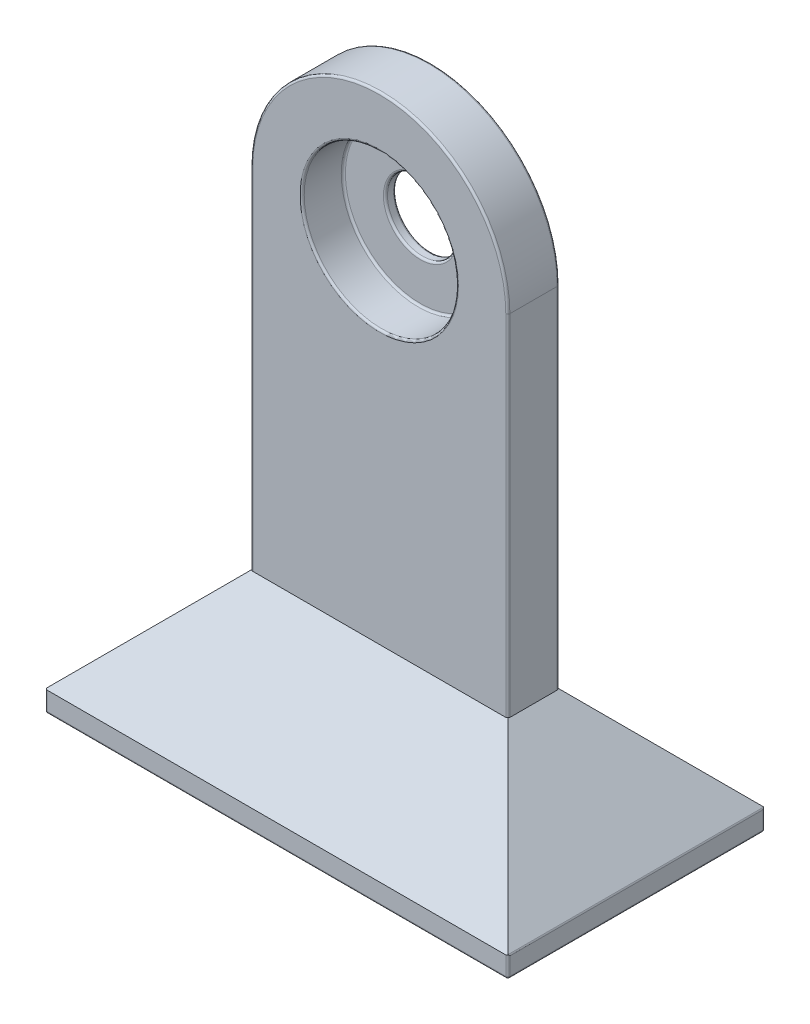
SolidWorks part; units mm, degrees
ref_plane "Front Plane" through (0, 0, 0) normal (0, 0, 1) x (1, 0, 0)
ref_plane "Top Plane" through (0, 0, 0) normal (0, 1, 0) x (1, 0, 0)
ref_plane "Right Plane" through (0, 0, 0) normal (1, 0, 0) x (0, 0, -1)
sketch "Sketch1" plane through (0, 0, 0) normal (0, 0, 1) x (1, 0, 0)
  line L0 (-12.5, 0) -> (-12.5, -34)
  line L8 (-12.5, -34) -> (12.5, -34)
  line L9 (12.5, -34) -> (12.5, 0)
  circle A1 centre (0, 0) radius 7.5
  arc A2 (12.5, 0) -> (-12.5, 0) centre (0, 0) ccw
  dimension "D1" = 15
  dimension "D2" = 25
  dimension "D3" = 34
extrude "Boss-Extrude1" add sketch "Sketch1" along normal mid plane 5
sketch "Sketch2" plane through (0, 0, -2.5) normal (0, 0, -1) x (-1, 0, 0)
  circle A0 centre (0, 0) radius 7.5
  circle A1 centre (0, 0) radius 7.5 construction
  circle A2 centre (0, 0) radius 3.4
  dimension "D1" = 6.8
extrude "Boss-Extrude2" add sketch "Sketch2" against normal blind 1
ref_plane "Plane1" through (0, -44, 0) normal (0, -1, 0) x (-1, 0, 0)
sketch "Sketch3" plane through (0, -34, 0) normal (0, -1, 0) x (1, 0, 0)
  line L1 (-12.5, 2.5) -> (12.5, 2.5)
  line L2 (-12.5, 2.5) -> (-12.5, -2.5)
  line L3 (-12.5, -2.5) -> (12.5, -2.5)
  line L4 (12.5, 2.5) -> (12.5, -2.5)
sketch "Sketch4" plane through (0, -44, 0) normal (0, -1, 0) x (-1, 0, 0)
  line L1 (-22.5, 12.5) -> (22.5, 12.5)
  line L2 (-22.5, 12.5) -> (-22.5, -12.5)
  line L3 (-22.5, -12.5) -> (22.5, -12.5)
  line L4 (22.5, 12.5) -> (22.5, -12.5)
  point P4 (22.5, 0)
  point P6 (0, 12.5)
  dimension "D1" = 25
  dimension "D2" = 45
loft "Loft1" add profiles "Sketch4", "Sketch3" connector at (22.5, -44, 12.5) connector at (12.5, -34, 2.5)
sketch "Sketch5" plane through (0, -44, 0) normal (0, -1, 0) x (1, 0, 0)
  line L1 (-22.5, 12.5) -> (22.5, 12.5)
  line L2 (-22.5, 12.5) -> (-22.5, -12.5)
  line L3 (-22.5, -12.5) -> (22.5, -12.5)
  line L4 (22.5, 12.5) -> (22.5, -12.5)
extrude "Boss-Extrude3" add sketch "Sketch5" along normal blind 2
fillet "Fillet2" radius 0.2 20 edges at (12.5, -17, 2.5) (-12.5, -17, 2.5) (12.5, -17, -2.5) (-12.5, -17, -2.5) (0, -46, 12.5) (22.5, -46, 0) (0, -46, -12.5) (-22.5, -46, 0) (-3.4, 0, -2.5) (-3.4, 0, -1.5) (-7.5, 0, -1.5) (7.5, 0, 2.5) (0, 12.5, 2.5) (0, 12.5, -2.5)
